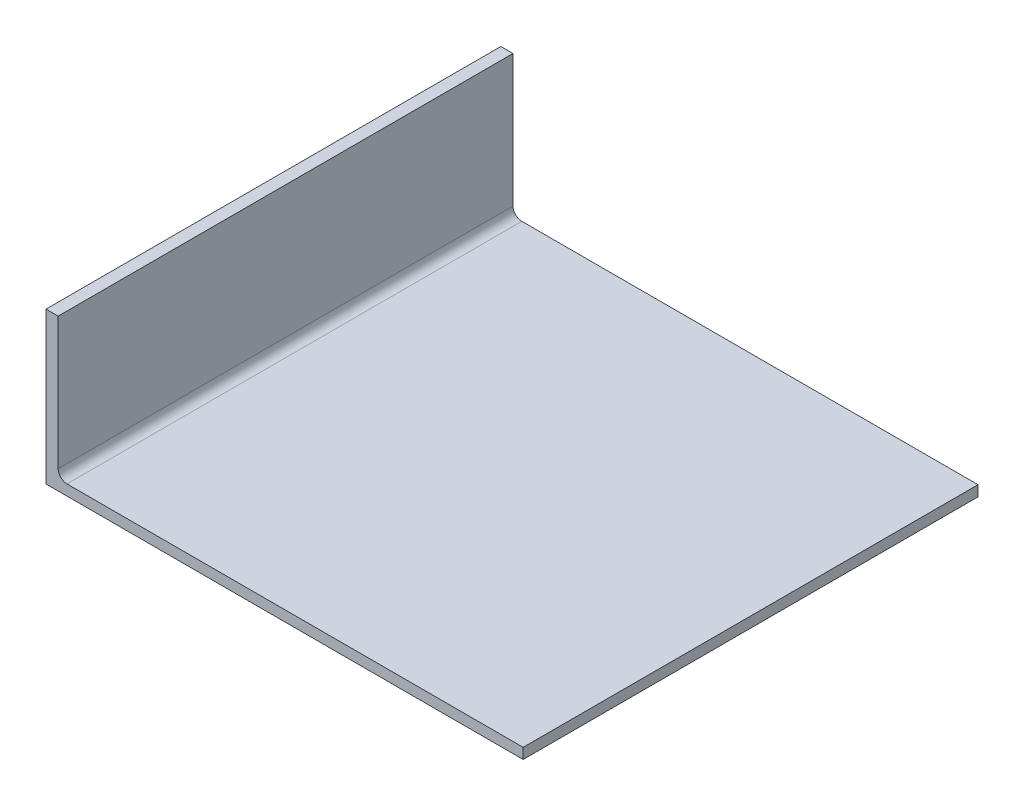
SolidWorks part; units mm, degrees
ref_plane "Front Plane" through (0, 0, 0) normal (0, 0, 1) x (1, 0, 0)
ref_plane "Top Plane" through (0, 0, 0) normal (0, 1, 0) x (1, 0, 0)
ref_plane "Right Plane" through (0, 0, 0) normal (1, 0, 0) x (0, 0, -1)
sketch "Sketch1" plane through (0, 0, 0) normal (0, 1, 0) x (1, 0, 0)
  line L1 (8.7553, 21.2243) -> (-262.1325, 21.2243)
  line L2 (8.7553, 21.2243) -> (8.7553, -236.9969)
  line L3 (8.7553, -236.9969) -> (-262.1325, -236.9969)
  line L6 (-262.1325, 21.2243) -> (-262.1325, -236.9969)
extrude "Base" add sketch "Sketch1" along normal blind 6
sketch "Sketch2" plane through (0, 6, 0) normal (0, 1, 0) x (1, 0, 0)
  line L0 (-262.1325, -236.9969) -> (8.7553, -236.9969) construction
  line L1 (-262.1325, 21.2243) -> (-255.2403, 21.2243)
  line L2 (-262.1325, 21.2243) -> (-262.1325, -236.9969)
  line L3 (-262.1325, -236.9969) -> (-255.2403, -236.9969)
  line L4 (-255.2403, 21.2243) -> (-255.2403, -236.9969)
extrude "Boss-Extrude2" add sketch "Sketch2" along normal blind 80
fillet "Fillet1" radius 5 1 edges at (-255.2403, 6, 107.8863) type face fillet first side face at (-255.2403, 46, 107.8863) second side face at (-123.2425, 6, 107.8863)
